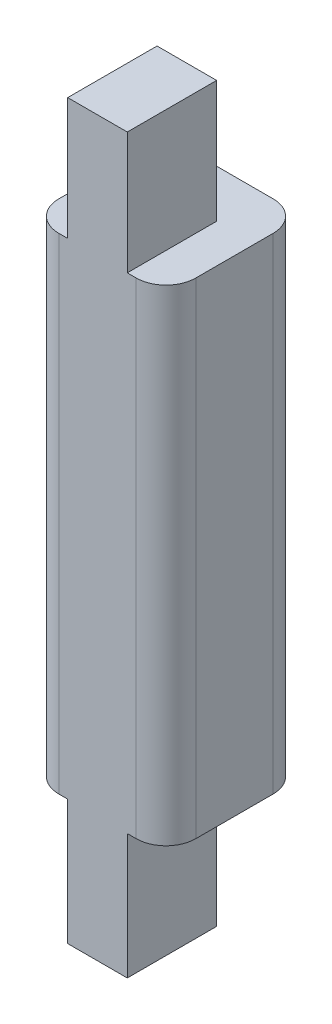
SolidWorks part; units mm, degrees
ref_plane "Front Plane" through (0, 0, 0) normal (0, 0, 1) x (1, 0, 0)
ref_plane "Top Plane" through (0, 0, 0) normal (0, 1, 0) x (1, 0, 0)
ref_plane "Right Plane" through (0, 0, 0) normal (1, 0, 0) x (0, 0, -1)
sketch "Sketch2" plane through (0, 0, 0) normal (0, 1, 0) x (1, 0, 0)
  line L0 (0, -11.5) -> (0, 11.5) construction
  line L1 (-11.5, -11.5) -> (11.5, -11.5)
  line L2 (-11.5, -11.5) -> (-11.5, 11.5)
  line L3 (-11.5, 11.5) -> (11.5, 11.5)
  line L4 (11.5, -11.5) -> (11.5, 11.5)
  line L5 (-11.5, -11.5) -> (11.5, 11.5) construction
  line L6 (-11.5, 11.5) -> (11.5, -11.5) construction
  line L7 (-5, -11.5) -> (5, -11.5)
  line L8 (-5, -11.5) -> (-5, 3.5)
  line L9 (-5, 3.5) -> (5, 3.5)
  line L10 (5, -11.5) -> (5, 3.5)
  point P0 (0, 0)
  point P10 (0, 3.5)
  point P13 (0, 0)
  dimension "D1" = 23
  dimension "D2" = 10
  dimension "D3" = 15
extrude "Boss-Extrude1" add sketch "Sketch2" along normal blind 81.5 contours L10 L1 L4 L3 L2 L8 L9 | L1 L10 L9 L8 region at (-11.1747, 0, 0) region at (0, 0, 4)
extrude "Boss-Extrude2" add sketch "Sketch2<3>" against normal blind 21 contours L1 L10 L9 L8 region at (0, 0, 4)
sketch "Sketch2<3>" plane through (0, 0, 0) normal (0, 1, 0) x (1, 0, 0) same geometry as "Sketch2"
sketch "Sketch3" plane through (11.5, 0, 0) normal (1, 0, 0) x (0, 0, -1)
  line L0 (-11.5, 81.5) -> (11.547, -0.5278) construction
  line L1 (-30.2664, 40.4861) -> (30.3134, 40.4861) construction
  point P6 (0.0235, 40.4861)
ref_plane "Plane1" through (0, 40.4861, 0) normal (0, 1, 0) x (1, 0, 0)
fillet "Fillet1" radius 5 4 edges at (-11.5, 40.75, 11.5) (11.5, 40.75, 11.5) (-11.5, 40.75, -11.5) (11.5, 40.75, -11.5)
mirror "Mirror1" about plane through (0, 40.4861, 0) normal (0, 1, 0) of "Boss-Extrude2"
